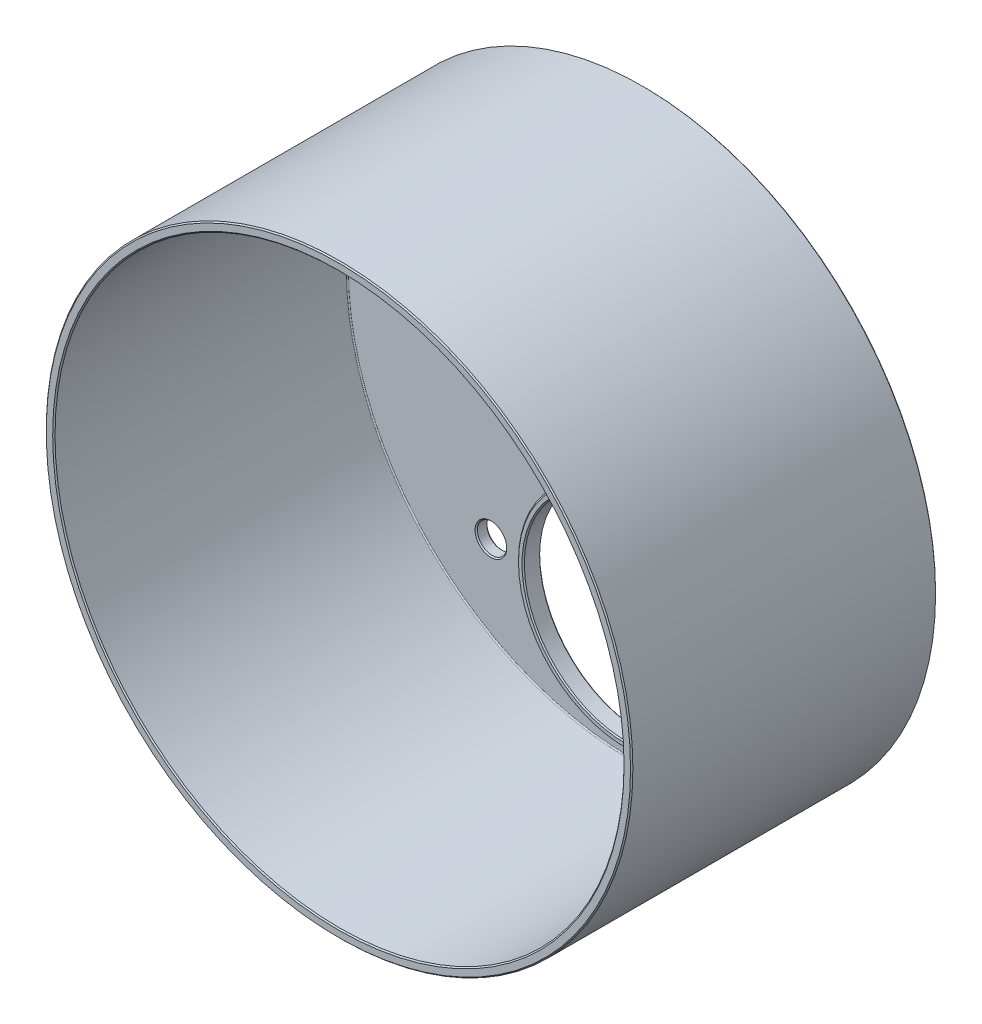
SolidWorks part; units mm, degrees
ref_plane "Спереди" through (0, 0, 0) normal (0, 0, 1) x (1, 0, 0)
ref_plane "Сверху" through (0, 0, 0) normal (0, 1, 0) x (1, 0, 0)
ref_plane "Справа" through (0, 0, 0) normal (1, 0, 0) x (0, 0, -1)
sketch "Эскиз1" plane through (0, 0, 0) normal (0, 0, 1) x (1, 0, 0)
  line L0 (0, 0) -> (0, -50000) construction
  line L1 (0, 0) -> (50000, 0) construction
  circle A13 centre (0, 0) radius 17.5
  circle A19 centre (0, 28) radius 50
  circle A20 centre (-24, 0) radius 2.5
  circle A21 centre (24, 0) radius 2.5
  circle A22 centre (0, 24) radius 2.5
  point P15 (0, 0)
  point P31 (0, 0)
  dimension "D1" = 5
  dimension "D2" = 5
  dimension "D3" = 24
  dimension "D4" = 100
  dimension "D6" = 35
  dimension "D7" = 24
  dimension "D8" = 5
  dimension "D5" = 28
  dimension "D9" = 24
extrude "Бобышка-Вытянуть1" add sketch "Эскиз1" along normal blind 2
sketch "Эскиз4" plane through (0, 0, 2) normal (0, 0, 1) x (1, 0, 0)
  circle A0 centre (0, 0) radius 17.5
  circle A1 centre (0, 0) radius 18.5
  dimension "D1" = 37
  dimension "D2" = 35
extrude "Бобышка-Вытянуть4" add sketch "Эскиз4" along normal blind 1
sketch "Эскиз5" plane through (0, 0, 2) normal (0, 0, 1) x (1, 0, 0)
  circle A0 centre (0, 0) radius 19.5
  circle A1 centre (0, 28) radius 50
  circle A2 centre (0, 28) radius 48.5
  dimension "D1" = 39
  dimension "D2" = 100
  dimension "D3" = 97
extrude "Бобышка-Вытянуть5" add sketch "Эскиз5" along normal blind 50 contours A2 | A1
fillet "Скругление5" radius 0.2 2 edges at (48.5, 28, 2) (18.5, 0, 2)
chamfer "Фаска8" distance 0.2 angle 45 12 edges at (17.5, 0, 3) (18.5, 0, 3) (2.5, 24, 0) (26.5, 0, 0) (-21.5, 0, 0) (17.5, 0, 0) (50, 28, 0) (48.5, 28, 52) (50, 28, 52) (2.5, 24, 2) (-21.5, 0, 2) (26.5, 0, 2)
